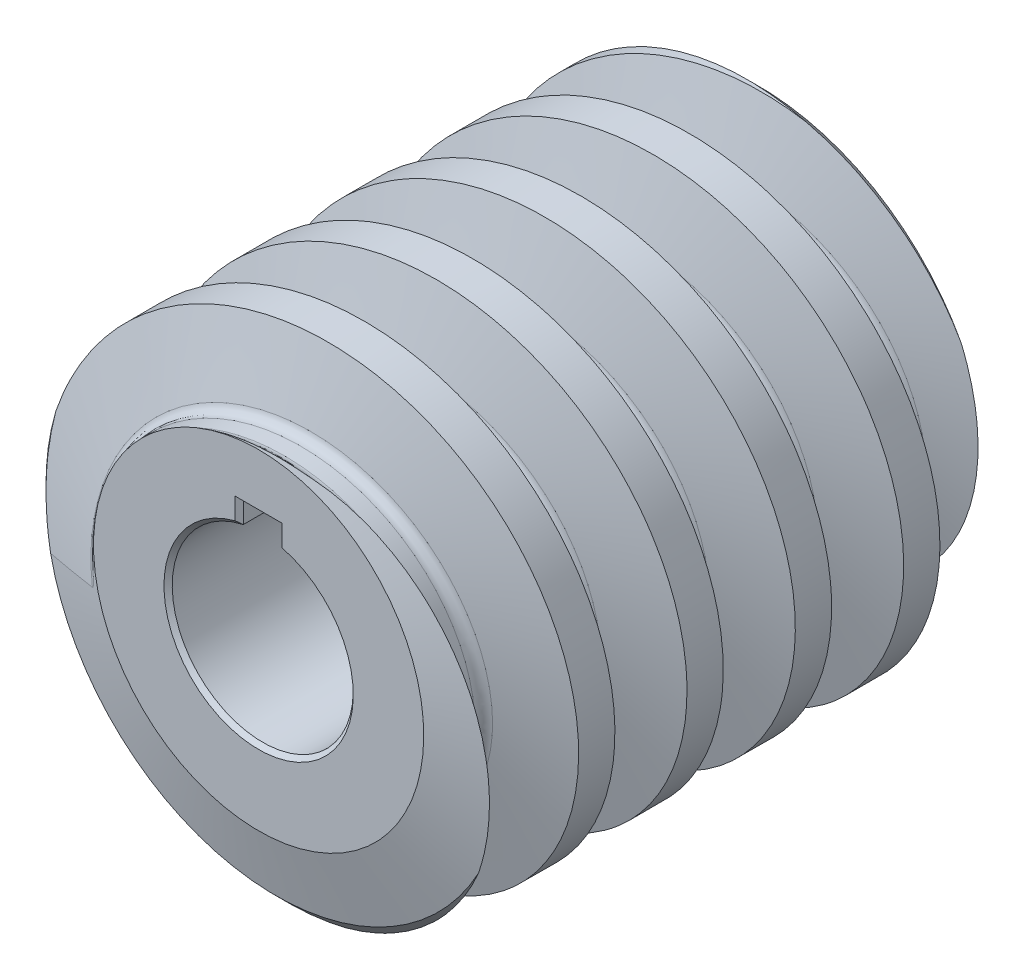
SolidWorks part; units mm, degrees
note: '?' marks a value the reader was unsure of.
ref_plane "Front" through (0, 0, 0) normal (0, 0, 1) x (1, 0, 0)
ref_plane "Top" through (0, 0, 0) normal (0, 1, 0) x (1, 0, 0)
ref_plane "Right" through (0, 0, 0) normal (1, 0, 0) x (0, 0, -1)
ref_axis "Axis1" through (0, 0, 55) along (0, 0, -1)?
sketch "SketchRevolveWorm01" plane through (0, 0, 0) normal (1, 0, 0) x (0, 0, -1)
  line L0 (0, 0) -> (25.4, 0) construction
  line L1 (31.75, 0) -> (31.75, 26.1027)
  line L2 (31.75, 26.1027) -> (28.2194, 29.6333)
  line L3 (28.2194, 29.6333) -> (-28.2194, 29.6333)
  line L4 (-28.2194, 29.6333) -> (-31.75, 26.1027)
  line L5 (-31.75, 26.1027) -> (-31.75, 0)
  line L6 (-31.75, 0) -> (31.75, 0)
  dimension "Side1" = 31.75
  dimension "ChamferX" = 3.5306
  dimension "ChamferY" = 3.5306
  dimension "OutsideDiameter" = 29.6333
  dimension "WormLength" = 63.5
revolve "Worm01" add sketch "SketchRevolveWorm01" angle 360 about L0
ref_plane "HelixPlaneWorm01" through (0, 0, 39.8982) normal (0, 0, 1) x (1, 0, 0)
sketch "SketchHelixWorm01" plane through (0, 0, 39.8982) normal (0, 0, 1) x (1, 0, 0)
  circle A0 centre (0, 0) radius 25.4
  dimension "PitchDiameter" = 50.8
curve "GearHelixWorm01" pitch 13.2994 height 79.7965 turns 6
sketch "SketchToothWorm01" plane through (0, 0, 0) normal (0, 1, 0) x (1, 0, 0)
  line L0 (30.6917, -35.1999) -> (21.2201, -37.6583)
  line L1 (20.2692, -38.8875) -> (20.2692, -40.9089)
  line L2 (21.2201, -42.1382) -> (30.6917, -44.5966)
  line L3 (30.6917, -44.5966) -> (30.6917, -35.1999)
  arc A0 (21.2201, -37.6583) -> (20.2692, -38.8875) centre (21.5392, -38.8875) ccw
  arc A1 (20.2692, -40.9089) -> (21.2201, -42.1382) centre (21.5392, -40.9089) ccw
sweep "ToothCutWorm01" cut profiles "SketchToothWorm01" path "GearHelixWorm01"
sketch "BoreRevolveSketch" plane through (0, 0, 0) normal (1, 0, 0) x (0, 0, -1)
  line L0 (0, 0) -> (25.4, 0) construction
  line L1 (-31.75, 0) -> (31.75, 0)
  line L2 (31.75, 0) -> (31.75, 11.1125)
  line L3 (31.75, 11.1125) -> (-31.75, 11.1125)
  line L4 (-31.75, 11.1125) -> (-31.75, 0)
  dimension "BoreSide1" = 31.75
  dimension "TaperSide1" = 11.1125
  dimension "BoreSide2" = 31.75
  dimension "TaperSide2" = 11.1125
revolve "BoreRevolveCut" cut sketch "BoreRevolveSketch" angle 360 about L0
sketch "KeywaySketch" plane through (0, 0, 0) normal (0, 0, 1) x (1, 0, 0)
  line L0 (0, 0) -> (0, 29.6333) construction
  line L1 (-2.3812, 13.3731) -> (-2.3812, 10.1981)
  line L2 (-2.3812, 10.1981) -> (2.3812, 10.1981)
  line L3 (2.3812, 10.1981) -> (2.3812, 13.3731)
  line L4 (2.3812, 13.3731) -> (-2.3812, 13.3731)
  circle A0 centre (0, 0) radius 29.6333 construction
  circle A1 centre (0, 0) radius 29.6333 construction
  circle A2 centre (0, 0) radius 11.1125 construction
  circle A3 centre (0, 0) radius 11.1125 construction
  point P7 (0, 10.1981)
  point P13 (0, 11.1125)
  point P14 (0, -11.1125)
  dimension "D1" = 3.175
  dimension "D2" = 4.7625
  dimension "D3" = 24.4856
extrude "Keyway" cut sketch "KeywaySketch" against normal through all and the other way through all
sketch "AuxiliarySketchWorm01" plane through (0, 0, 0) normal (0, 0, 1) x (1, 0, 0)
  circle A0 centre (0, 0) radius 25.4 construction
  dimension "PitchDiameter" = 50.8
sketch "Sketch7" plane through (0, 0, 31.75) normal (0, 0, 1) x (1, 0, 0)
  circle A0 centre (0, 0) radius 20.2692
  arc A1 (-7.6154, 18.7842) -> (-19.7344, 4.6252) centre (0, 0) ccw construction
extrude "Cut-Extrude2" cut sketch "Sketch7" against normal blind 2.54 draft 75 flip side to cut
mirror "Mirror1" about plane through (0, 0, 0) normal (0, 0, 1) of "Cut-Extrude2"
chamfer "Chamfer1" distance 0.508 angle 45 8 edges at (-2.3812, 12.1137, -31.75) (0, 13.3731, -31.75) (2.3812, 12.1137, -31.75) (0, -11.1125, -31.75) (2.3812, 12.1137, 31.75) (0, 13.3731, 31.75) (-2.3812, 12.1137, 31.75) (0, -11.1125, 31.75)
